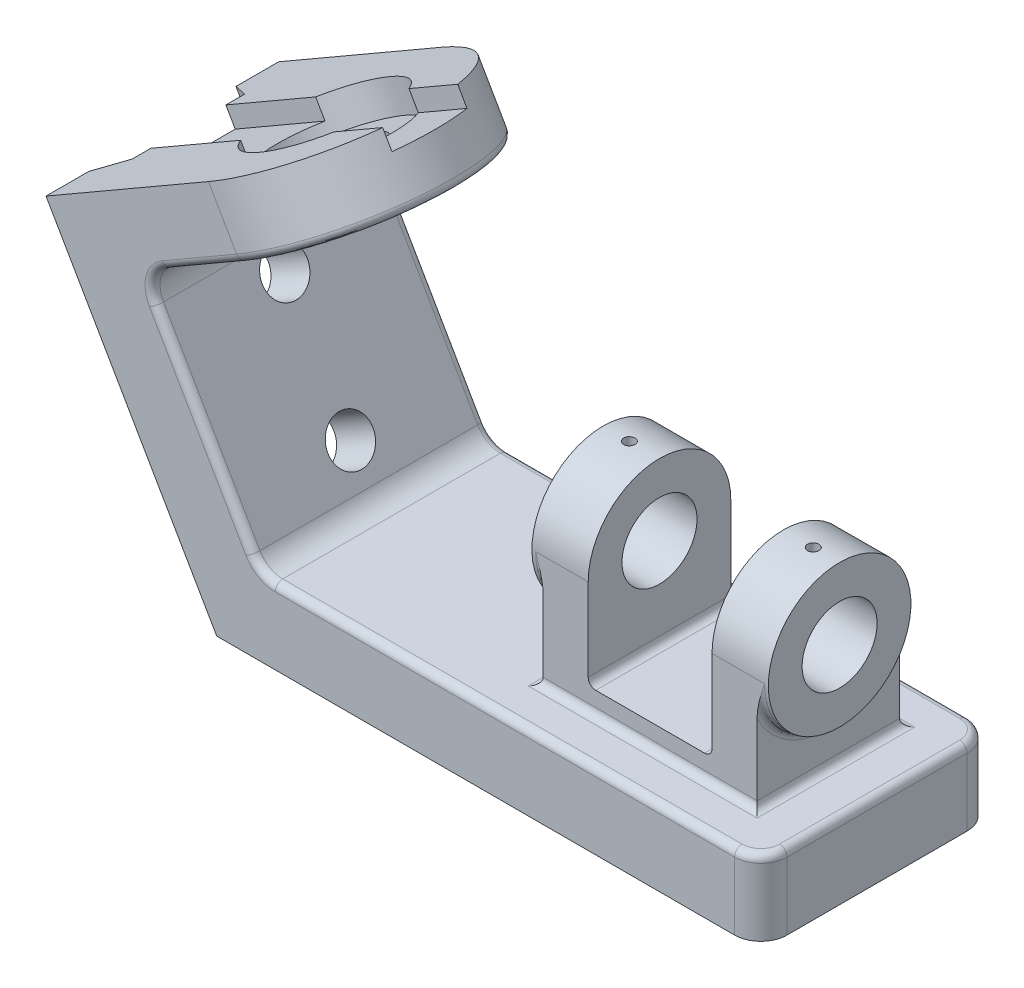
SolidWorks part; units mm, degrees
material "Plain Carbon Steel"
ref_plane "Front Plane" through (0, 0, 0) normal (0, 0, 1) x (1, 0, 0)
ref_plane "Top Plane" through (0, 0, 0) normal (0, 1, 0) x (1, 0, 0)
ref_plane "Right Plane" through (0, 0, 0) normal (1, 0, 0) x (0, 0, -1)
sketch "Sketch1" plane through (0, 0, 0) normal (0, 0, 1) x (1, 0, 0)
  line L0 (0, 0) -> (145, 0)
  line L1 (145, 0) -> (145, 20)
  line L2 (145, 20) -> (11.547, 20)
  line L3 (11.547, 20) -> (-19.6795, 74.0859)
  line L4 (-19.6795, 74.0859) -> (6.3013, 89.0859)
  line L5 (6.3013, 89.0859) -> (-2.1987, 103.8083)
  line L6 (-2.1987, 103.8083) -> (-45.5, 78.8083)
  line L7 (-45.5, 78.8083) -> (0, 0)
  dimension "D1" = 20
  dimension "D2" = 17
  dimension "D3" = 60
  dimension "D4" = 20
  dimension "D5" = 91
  dimension "D6" = 145
  dimension "D7" = 50
extrude "Boss-Extrude1" add sketch "Sketch1" along normal mid plane 62
sketch "Sketch2" plane through (-45.5, 78.8083, 0) normal (-0.5, 0.866, 0) x (0.866, 0.5, 0)
  line L0 (50, -31) -> (50, 31) construction
  line L1 (50, 31) -> (50, -31)
  arc A0 (50, -31) -> (50, 31) centre (50, 0) ccw
extrude "Boss-Extrude2" add sketch "Sketch2" against normal blind 17
sketch "Sketch3" plane through (0, 20, 0) normal (0, 1, 0) x (1, 0, 0)
  line L0 (145, -31) -> (145, 31) construction
  line L1 (132, 19) -> (75, 19)
  line L2 (132, 19) -> (132, -19)
  line L3 (132, -19) -> (75, -19)
  line L4 (75, 19) -> (75, -19)
  line L5 (145, 0) -> (38.6863, 0) construction
  point P9 (132, 0)
  dimension "D1" = 57
  dimension "D2" = 38
  dimension "D3" = 13
extrude "Boss-Extrude3" add sketch "Sketch3" along normal blind 6
sketch "Sketch5" plane through (132, 0, 0) normal (1, 0, 0) x (0, 0, -1)
  line L0 (-19, 26) -> (19, 26)
  line L1 (-19, 26) -> (19, 26) construction
  line L2 (-19, 50) -> (19, 50)
  line L3 (19, 50) -> (19, 26)
  line L4 (19, 26) -> (19, 20) construction
  line L5 (-19, 50) -> (-19, 26)
  dimension "D1" = 24
extrude "Boss-Extrude4" add sketch "Sketch5" against normal blind 12
sketch "Sketch6" plane through (75, 0, 0) normal (-1, 0, 0) x (0, 0, 1)
  line L0 (19, 26) -> (-19, 26)
  line L1 (-19, 26) -> (-19, 50)
  line L2 (-19, 50) -> (19, 50)
  line L3 (19, 50) -> (19, 26)
  dimension "D1" = 24
extrude "Boss-Extrude5" add sketch "Sketch6" against normal blind 12
sketch "Sketch8" plane through (120, 0, 0) normal (-1, 0, 0) x (0, 0, 1)
  line L0 (-19, 50) -> (19, 50) construction
  circle A0 centre (0, 50) radius 19
  circle A1 centre (0, 50) radius 10
  dimension "D1" = 38
  dimension "D2" = 20
extrude "Boss-Extrude6" add sketch "Sketch8" against normal blind 15
sketch "Sketch9" plane through (135, 0, 0) normal (1, 0, 0) x (0, 0, -1)
  line L0 (10, 50) -> (-10, 50) construction
  circle A0 centre (0, 50) radius 10
  dimension "D1" = 20
extrude "Cut-Extrude1" cut sketch "Sketch9" against normal blind 15
sketch "Sketch10" plane through (87, 0, 0) normal (1, 0, 0) x (0, 0, -1)
  line L0 (-19, 50) -> (19, 50) construction
  circle A0 centre (0, 50) radius 19
  circle A1 centre (0, 50) radius 10
  dimension "D1" = 20
extrude "Boss-Extrude7" add sketch "Sketch10" against normal blind 15
sketch "Sketch12" plane through (87, 0, 0) normal (1, 0, 0) x (0, 0, -1)
  line L0 (-10, 50) -> (10, 50) construction
  circle A0 centre (0, 50) radius 10
  dimension "D1" = 20
extrude "Cut-Extrude2" cut sketch "Sketch12" against normal blind 15
sketch "Sketch13" [suppressed] plane through (-44, 76.2102, 0) normal (-0.5, 0.866, 0) x (0.866, 0.5, 0)
  line L0 (0, -30) -> (0, 30) construction
  line L1 (0, -10) -> (80, -10)
  line L2 (0, -10) -> (0, 10)
  line L3 (0, 10) -> (80, 10)
  line L4 (80, -10) -> (80, 10)
  arc A0 (50, -30) -> (50, 30) centre (50, 0) ccw construction
  point P9 (80, 0)
  point P10 (80, 0)
  dimension "D1" = 20
extrude "Cut-Extrude3" [suppressed] cut sketch "Sketch13" against normal blind 5
sketch "Sketch14" [suppressed] plane through (-44, 76.2102, 0) normal (-0.5, 0.866, 0) x (0.866, 0.5, 0)
  line L0 (0, -19.6188) -> (8, -15)
  line L1 (0, -30) -> (0, -10) construction
  line L2 (8, -15) -> (8, -10)
  line L3 (0, -10) -> (78.2843, -10) construction
  line L4 (0, 19.6188) -> (8, 15)
  line L5 (0, 10) -> (0, 30) construction
  line L6 (8, 15) -> (8, 10)
  line L7 (78.2843, 10) -> (0, 10) construction
  line L8 (8, 10) -> (8, -10)
  line L9 (0, -19.6188) -> (0, 19.6188)
  dimension "D1" = 30
  dimension "D2" = 8
  dimension "D3" = 30
  dimension "D4" = 8
  dimension "D5" = 30
extrude "Cut-Extrude4" [suppressed] cut sketch "Sketch14" against normal through all
sketch "Sketch15" plane through (-45.5, 78.8083, 0) normal (-0.5, 0.866, 0) x (0.866, 0.5, 0)
  line L0 (0, 10) -> (79.3428, 10)
  line L1 (0, -31) -> (0, 31) construction
  line L2 (0, -10) -> (79.3428, -10)
  line L3 (0, 10) -> (0, -10)
  line L4 (79.3428, 10) -> (81.4477, 10)
  line L5 (81.4477, 10) -> (81.4477, -10)
  line L6 (81.4477, -10) -> (79.3428, -10)
  arc A0 (50, -31) -> (50, 31) centre (50, 0) ccw construction
  point P9 (0, 0)
  point P10 (0, 0)
  dimension "D1" = 20
extrude "Cut-Extrude5" cut sketch "Sketch15" against normal blind 5
sketch "Sketch16" plane through (-45.5, 78.8083, 0) normal (-0.5, 0.866, 0) x (0.866, 0.5, 0)
  line L0 (8, 10) -> (8, 15)
  line L4 (79.3428, 10) -> (0, 10) construction
  line L5 (8, 15) -> (0, 19.6188)
  line L6 (0, 10) -> (0, 31) construction
  line L7 (79.3428, 10) -> (0, 10) construction
  line L8 (8, -10) -> (8, -15)
  line L9 (0, -10) -> (79.3428, -10) construction
  line L10 (8, -15) -> (0, -19.6188)
  line L11 (0, -31) -> (0, -10) construction
  line L12 (0, 19.6188) -> (0, 10)
  line L14 (0, -19.6188) -> (0, -10)
  line L16 (0, 10) -> (0, -10)
  line L17 (8, -10) -> (8, 10)
  dimension "D1" = 30
  dimension "D2" = 30
  dimension "D3" = 8
  dimension "D4" = 8
extrude "Cut-Extrude7" cut sketch "Sketch16" against normal through all
sketch "Sketch18" plane through (-45.5, 78.8083, 0) normal (-0.5, 0.866, 0) x (0.866, 0.5, 0)
  line L0 (8, -10) -> (8, 10) construction
  circle A0 centre (50, 0) radius 17.5
  circle A1 centre (50, 0) radius 10
  point P7 (8, 0)
  dimension "D1" = 35
  dimension "D2" = 20
extrude "Cut-Extrude8" cut sketch "Sketch18" against normal blind 8
sketch "Sketch20" plane through (-43, 74.4782, 0) normal (-0.5, 0.866, 0) x (0.866, 0.5, 0)
  circle A0 centre (50, 0) radius 10
  dimension "D1" = 20
extrude "Cut-Extrude9" cut sketch "Sketch20" against normal blind 38
sketch "Sketch21" plane through (6.9282, 4, 0) normal (-0.866, -0.5, 0) x (0, 0, 1)
  line L0 (15, -4.6188) -> (-15, -4.6188) construction
  circle A0 centre (0, 60.3812) radius 6
  circle A1 centre (0, 25.3812) radius 6
  dimension "D1" = 12
  dimension "D2" = 30
  dimension "D3" = 35
extrude "Cut-Extrude10" cut sketch "Sketch21" against normal blind 38
fillet "Fillet1" radius 7 4 edges at (145, 10, -31) (145, 10, 31) (-19.6795, 74.0859, 0) (11.547, 20, 0)
fillet "Fillet2" radius 2 22 edges at (12.0885, 20.9378, 31) (-3.3266, 45.7619, 31) (-16.8788, 73.3354, 31) (-3.658, 83.3359, 31) (33.1481, 104.5859, 0) (-3.658, 83.3359, -31) (-16.8788, 73.3354, -31) (-3.3266, 45.7619, -31) (12.0885, 20.9378, -31) (103.5, 20, -19) (75, 20, 0) (103.5, 20, 19) (132, 20, 0) (142.9497, 20, 28.9497) (76.7942, 20, 31) (76.7942, 20, -31) (142.9497, 20, -28.9497) (145, 20, 0) (75, 31, 0) (132, 31, 0) (120, 26, 0) (87, 26, 0)
ref_plane "Plane1" through (0, 69, 0) normal (0, 1, 0) x (1, 0, 0)
sketch "Sketch22" plane through (0, 69, 0) normal (0, 1, 0) x (1, 0, 0)
  line L0 (72, 19) -> (72, -33.9342) construction
  line L1 (135, 23.8263) -> (135, -35.9395) construction
  line L2 (135, -19) -> (135, 19) construction
  circle A0 centre (79, 0) radius 1.5
  circle A1 centre (128, 0) radius 1.5
  dimension "D1" = 3
  dimension "D2" = 7
  dimension "D3" = 7
extrude "Cut-Extrude11" cut sketch "Sketch22" against normal blind 11
sketch3d "3DSketch1" [suppressed]
  point P0 (2.6241, 11.4549, 3.4951)
equation "\"A\"= 145"
equation "\"B\"= 91"
equation "\"C\"= 31"
equation "\"D5@Sketch1\"=\"B\""
equation "\"D6@Sketch1\"=\"A\""
equation "\"D1@Boss-Extrude1\"=\"C\"*2"
